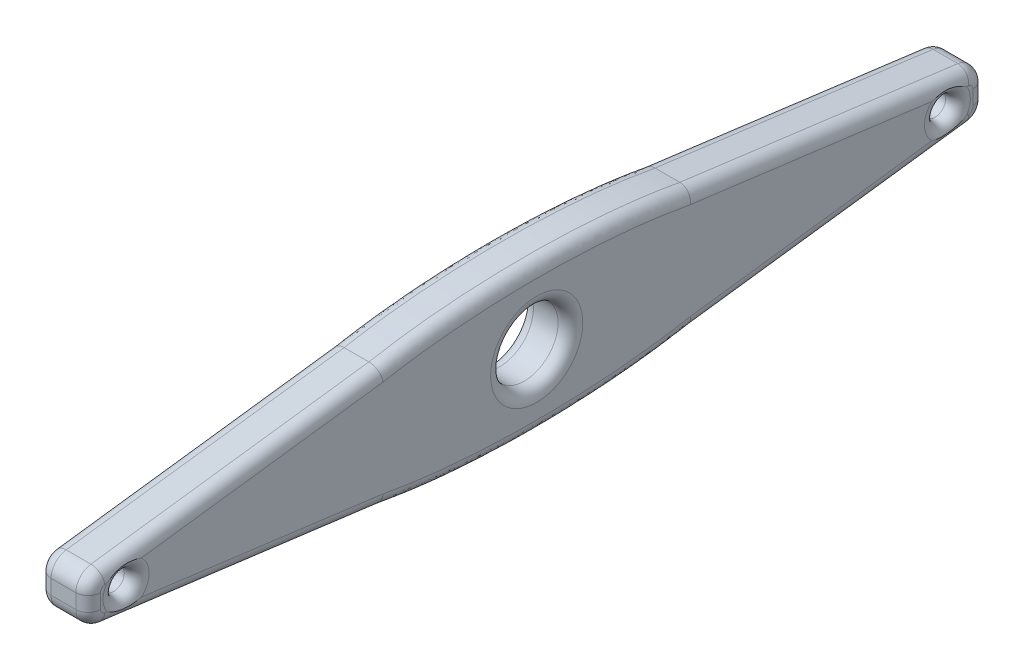
SolidWorks part; units mm, degrees
ref_plane "Front Plane" through (0, 0, 0) normal (0, 0, 1) x (1, 0, 0)
ref_plane "Top Plane" through (0, 0, 0) normal (0, 1, 0) x (1, 0, 0)
ref_plane "Right Plane" through (0, 0, 0) normal (1, 0, 0) x (0, 0, -1)
sketch "Sketch2" plane through (0, 0, 0) normal (1, 0, 0) x (0, 0, -1)
  line L0 (-87.6524, 4.9491) -> (-31.4438, 12.2633) construction
  line L6 (-90.7008, 1.4784) -> (-90.7008, -1.4784)
  line L9 (90.7008, 1.4784) -> (90.7008, -1.4784)
  line L10 (87.6524, 4.9491) -> (31.4438, 12.2633)
  line L11 (0, 14.9214) -> (0, -14.9214) construction
  line L12 (-90.7008, 0) -> (90.7008, 0) construction
  line L13 (-87.6524, 4.9491) -> (-31.4438, 12.2633)
  line L14 (87.6524, -4.9491) -> (31.4438, -12.2633)
  line L15 (-87.6524, -4.9491) -> (-31.4438, -12.2633)
  arc A0 (-87.6524, 4.9491) -> (-90.7008, 1.4784) centre (-87.2008, 1.4784) ccw
  arc A1 (87.6524, 4.9491) -> (90.7008, 1.4784) centre (87.2008, 1.4784) cw
  arc A2 (87.6524, -4.9491) -> (90.7008, -1.4784) centre (87.2008, -1.4784) ccw
  arc A3 (-87.6524, -4.9491) -> (-90.7008, -1.4784) centre (-87.2008, -1.4784) cw
  ellipse E0 centre (0, 0) end of major axis (55.195, 0) minor radius 14.9214 (31.4438, 12.2633) -> (-31.4438, 12.2633) ccw
  ellipse E1 centre (0, 0) end of major axis (55.195, 0) minor radius 14.9214 (31.4438, -12.2633) -> (-31.4438, -12.2633) cw
  dimension "D1" = 3.5
extrude "Boss-Extrude1" add sketch "Sketch2" along normal blind 10
sketch "Sketch3" plane through (10, 0, 0) normal (1, 0, 0) x (0, 0, -1)
  line L0 (0, 0) -> (0, 14.9214) construction
  circle A0 centre (0, 0) radius 6.8203
  circle A1 centre (83.0431, 0) radius 2.1403
  circle A2 centre (-83.0431, 0) radius 2.1403
  ellipse E0 centre (0, 0) end of major axis (55.195, 0) minor radius 14.9214 (31.4438, 12.2633) -> (-31.4438, 12.2633) ccw construction
extrude "Cut-Extrude1" cut sketch "Sketch3" against normal blind 10
fillet "Fillet1" radius 2.5 30 edges at (0, 0, 90.7008) (0, -3.7881, 89.8305) (0, -8.6062, 59.5481) (0, -14.9214, 0) (0, -8.6062, -59.5481) (0, -3.7881, -89.8305) (0, 0, -90.7008) (0, 3.7881, -89.8305) (0, 8.6062, -59.5481) (0, 14.9214, 0) (0, 8.6062, 59.5481) (0, 3.7881, 89.8305) (0, 0, -6.8203) (0, 0, -85.1835) (0, 0, 85.1835) (10, 8.6062, 59.5481) (10, 14.9214, 0) (10, 8.6062, -59.5481) (10, 3.7881, -89.8305) (10, 0, -90.7008) (10, -3.7881, -89.8305) (10, -8.6062, -59.5481) (10, -14.9214, 0) (10, -8.6062, 59.5481) (10, -3.7881, 89.8305) (10, 0, 90.7008) (10, 3.7881, 89.8305) (10, 0, -6.8203) (10, 0, -85.1835) (10, 0, 85.1835)
